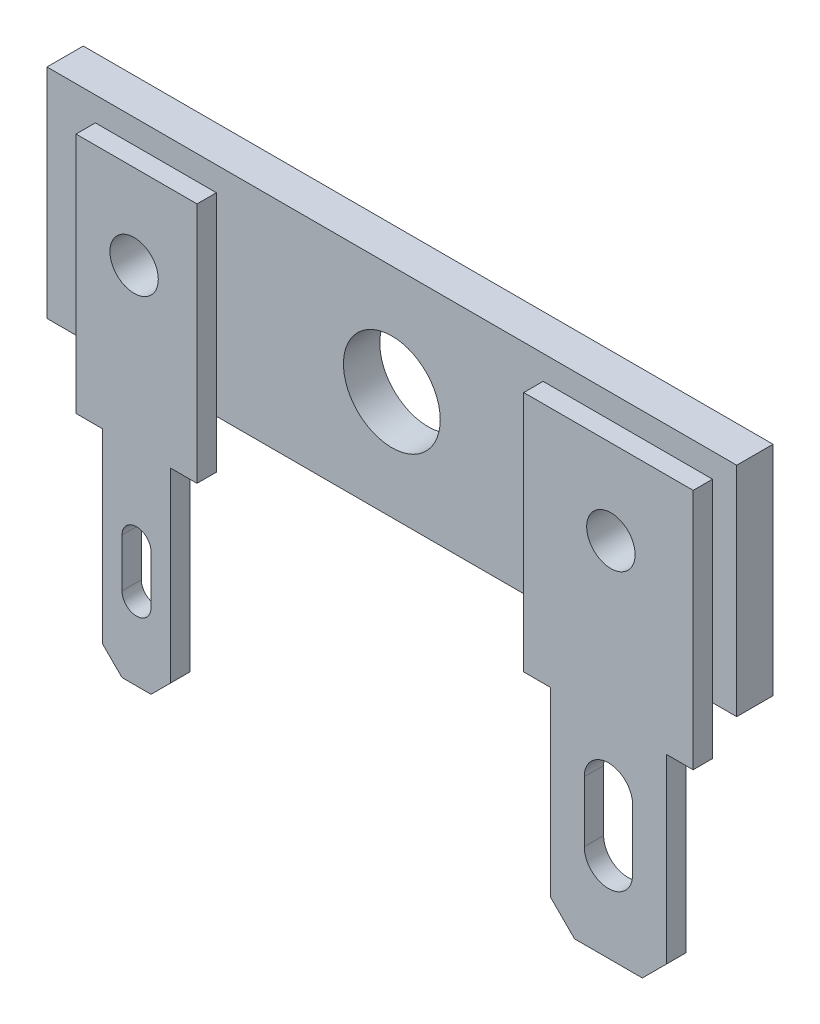
SolidWorks part; units mm, degrees
ref_plane "Plan de face" through (0, 0, 0) normal (0, 0, 1) x (1, 0, 0)
ref_plane "Plan de dessus" through (0, 0, 0) normal (0, 1, 0) x (1, 0, 0)
ref_plane "Plan de droite" through (0, 0, 0) normal (1, 0, 0) x (0, 0, -1)
sketch "Esquisse1" plane through (0, 0, 0) normal (0, 0, 1) x (1, 0, 0)
  line L0 (-54.543, 20.317) -> (-54.543, 30.317)
  line L1 (-54.543, 30.317) -> (-61.543, 30.317)
  line L2 (-61.543, 30.317) -> (-61.543, 20.317)
  line L3 (-61.543, 20.317) -> (-60.443, 20.317)
  line L4 (-60.443, 20.317) -> (-60.443, 12.817)
  line L5 (-60.443, 12.817) -> (-59.443, 11.817)
  line L6 (-59.443, 11.817) -> (-56.643, 11.817)
  line L7 (-56.643, 11.817) -> (-55.643, 12.817)
  line L8 (-55.643, 12.817) -> (-55.643, 20.317)
  line L9 (-55.643, 20.317) -> (-54.543, 20.317)
  line L10 (-75.043, 20.317) -> (-75.043, 30.317)
  line L11 (-75.043, 30.317) -> (-80.043, 30.317)
  line L12 (-80.043, 30.317) -> (-80.043, 20.317)
  line L13 (-80.043, 20.317) -> (-78.943, 20.317)
  line L14 (-78.943, 20.317) -> (-78.943, 12.617)
  line L15 (-78.943, 12.617) -> (-78.143, 11.817)
  line L16 (-78.143, 11.817) -> (-76.943, 11.817)
  line L17 (-76.943, 11.817) -> (-76.143, 12.617)
  line L18 (-76.143, 12.617) -> (-76.143, 20.317)
  line L19 (-76.143, 20.317) -> (-75.043, 20.317)
  line L20 (-82.043, 31.317) -> (-82.043, 22.317)
  line L21 (-82.043, 22.317) -> (-53.543, 22.317)
  line L22 (-53.543, 22.317) -> (-53.543, 31.317)
  line L23 (-53.543, 31.317) -> (-82.043, 31.317)
  line L24 (-76.943, 16.917) -> (-76.943, 14.917)
  line L25 (-78.143, 14.917) -> (-78.143, 16.917)
  line L26 (-57.043, 17.817) -> (-57.043, 15.317)
  line L27 (-59.043, 15.317) -> (-59.043, 17.817)
  arc A0 (-76.943, 14.917) -> (-78.143, 14.917) centre (-77.543, 14.917) cw
  arc A1 (-78.143, 16.917) -> (-76.943, 16.917) centre (-77.543, 16.917) cw
  arc A2 (-59.043, 17.817) -> (-57.043, 17.817) centre (-58.043, 17.817) cw
  arc A3 (-57.043, 15.317) -> (-59.043, 15.317) centre (-58.043, 15.317) cw
  arc A4 (-56.943, 26.817) -> (-58.943, 26.817) centre (-57.943, 26.817) cw
  arc A5 (-58.943, 26.817) -> (-56.943, 26.817) centre (-57.943, 26.817) cw
  arc A6 (-78.643, 26.817) -> (-76.643, 26.817) centre (-77.643, 26.817) cw
  arc A7 (-76.643, 26.817) -> (-78.643, 26.817) centre (-77.643, 26.817) cw
  arc A8 (-65.793, 26.817) -> (-69.793, 26.817) centre (-67.793, 26.817) cw
  arc A9 (-69.793, 26.817) -> (-65.793, 26.817) centre (-67.793, 26.817) cw
extrude "Boss.-Extru.1" add sketch "Esquisse1" along normal blind 1.5 contours L22 L23 L20 L21 L12 L11 L10 L2 L1 L0 A8 A9 | L21 L2 L3 L4 L5 L6 L7 L8 L9 L0 L26 A3 L27 A2 | L21 L12 L13 L14 L15 L16 L17 L18 L19 L10 L25 A1 L24 A0 | L2 L21 L0 L1 A4 A5 | L12 L21 L10 L11 A6 A7 region at (-55.093, 20.4432, 0) region at (-58.043, 22.4233, 0) region at (-54.2442, 26.317, 0) region at (-77.543, 22.4113, 0) region at (-77.543, 17.9428, 0)
sketch "Esquisse2" plane through (0, 0, 1.5) normal (0, 0, 1) x (1, 0, 0)
  line L0 (-80.043, 20.317) -> (-80.043, 30.317)
  line L1 (-75.043, 20.317) -> (-75.043, 30.317)
  line L2 (-80.043, 30.317) -> (-75.043, 30.317)
  line L3 (-61.543, 20.317) -> (-61.543, 30.317)
  line L4 (-54.543, 20.317) -> (-54.543, 30.317)
  line L5 (-61.543, 30.317) -> (-54.543, 30.317)
  line L6 (-76.143, 20.317) -> (-75.043, 20.317) construction
  line L7 (-80.043, 20.317) -> (-78.943, 20.317) construction
  line L8 (-78.943, 20.317) -> (-78.943, 12.617) construction
  line L9 (-78.943, 12.617) -> (-78.143, 11.817) construction
  line L10 (-78.143, 11.817) -> (-76.943, 11.817) construction
  line L11 (-76.943, 11.817) -> (-76.143, 12.617) construction
  line L12 (-76.143, 12.617) -> (-76.143, 20.317) construction
  line L13 (-76.943, 16.917) -> (-76.943, 14.917) construction
  line L14 (-78.143, 14.917) -> (-78.143, 16.917) construction
  line L15 (-61.543, 20.317) -> (-60.443, 20.317) construction
  line L16 (-60.443, 20.317) -> (-60.443, 12.817) construction
  line L17 (-55.643, 12.817) -> (-55.643, 20.317) construction
  line L18 (-55.643, 20.317) -> (-54.543, 20.317) construction
  line L19 (-57.043, 17.817) -> (-57.043, 15.317) construction
  line L20 (-59.043, 15.317) -> (-59.043, 17.817) construction
  line L21 (-76.143, 20.317) -> (-75.043, 20.317)
  line L22 (-80.043, 20.317) -> (-78.943, 20.317)
  line L23 (-78.943, 20.317) -> (-78.943, 12.617)
  line L24 (-78.943, 12.617) -> (-78.143, 11.817)
  line L25 (-78.143, 11.817) -> (-76.943, 11.817)
  line L26 (-76.943, 11.817) -> (-76.143, 12.617)
  line L27 (-76.143, 12.617) -> (-76.143, 20.317)
  line L28 (-76.943, 16.917) -> (-76.943, 14.917)
  line L29 (-78.143, 14.917) -> (-78.143, 16.917)
  line L30 (-61.543, 20.317) -> (-60.443, 20.317)
  line L31 (-60.443, 20.317) -> (-60.443, 12.817)
  line L32 (-55.643, 12.817) -> (-55.643, 20.317)
  line L33 (-55.643, 20.317) -> (-54.543, 20.317)
  line L34 (-57.043, 17.817) -> (-57.043, 15.317)
  line L35 (-59.043, 15.317) -> (-59.043, 17.817)
  arc A0 (-78.143, 14.917) -> (-76.943, 14.917) centre (-77.543, 14.917) ccw construction
  arc A1 (-76.943, 16.917) -> (-78.143, 16.917) centre (-77.543, 16.917) ccw construction
  arc A2 (-59.043, 15.317) -> (-57.043, 15.317) centre (-58.043, 15.317) ccw construction
  arc A3 (-57.043, 17.817) -> (-59.043, 17.817) centre (-58.043, 17.817) ccw construction
  arc A4 (-78.143, 14.917) -> (-76.943, 14.917) centre (-77.543, 14.917) ccw
  arc A5 (-76.943, 16.917) -> (-78.143, 16.917) centre (-77.543, 16.917) ccw
  arc A6 (-59.043, 15.317) -> (-57.043, 15.317) centre (-58.043, 15.317) ccw
  arc A7 (-57.043, 17.817) -> (-59.043, 17.817) centre (-58.043, 17.817) ccw
  circle A8 centre (-57.943, 26.817) radius 1 construction
  circle A9 centre (-77.643, 26.817) radius 1 construction
  circle A10 centre (-57.943, 26.817) radius 1
  circle A11 centre (-77.643, 26.817) radius 1
  line M16 (-61.543, 22.317) -> (-61.543, 20.317)
  line M17 (-61.543, 20.317) -> (-60.443, 20.317)
  line M18 (-60.443, 20.317) -> (-60.443, 12.817)
  line M19 (-60.443, 12.817) -> (-59.443, 11.817)
  line M20 (-59.443, 11.817) -> (-56.643, 11.817)
  line M21 (-56.643, 11.817) -> (-55.643, 12.817)
  line M22 (-55.643, 12.817) -> (-55.643, 20.317)
  line M23 (-55.643, 20.317) -> (-54.543, 20.317)
  line M24 (-54.543, 20.317) -> (-54.543, 22.317)
  line M30 (-80.043, 22.317) -> (-80.043, 20.317)
  line M31 (-80.043, 20.317) -> (-78.943, 20.317)
  line M32 (-78.943, 20.317) -> (-78.943, 12.617)
  line M33 (-78.943, 12.617) -> (-78.143, 11.817)
  line M34 (-78.143, 11.817) -> (-76.943, 11.817)
  line M35 (-76.943, 11.817) -> (-76.143, 12.617)
  line M36 (-76.143, 12.617) -> (-76.143, 20.317)
  line M37 (-76.143, 20.317) -> (-75.043, 20.317)
  line M38 (-75.043, 20.317) -> (-75.043, 22.317)
  line M39 (-78.143, 14.917) -> (-78.143, 16.917)
  arc M40 (-78.143, 16.917) -> (-76.943, 16.917) centre (-77.543, 16.917) cw
  line M41 (-76.943, 16.917) -> (-76.943, 14.917)
  arc M42 (-76.943, 14.917) -> (-78.143, 14.917) centre (-77.543, 14.917) cw
  circle M43 centre (-77.643, 26.817) radius 1
  circle M45 centre (-57.943, 26.817) radius 1
  line M46 (-57.043, 17.817) -> (-57.043, 15.317)
  arc M47 (-57.043, 15.317) -> (-59.043, 15.317) centre (-58.043, 15.317) cw
  line M48 (-59.043, 15.317) -> (-59.043, 17.817)
  arc M49 (-59.043, 17.817) -> (-57.043, 17.817) centre (-58.043, 17.817) cw
extrude "Boss.-Extru.2" add sketch "Esquisse2" along normal blind 0.8 contours L2 L0 L1 M30 M31 M32 M33 M34 M35 M36 M37 M38 M42 M39 M40 M41 M43 | L5 L3 L4 M16 M17 M18 M19 M20 M21 M22 M23 M24 M49 M46 M47 M48 M45 region at (-77.5383, 22.5616, 1.5) region at (-58.0462, 22.2951, 1.5)
sketch "Esquisse3" plane through (-82.043, 0, 0) normal (-1, 0, 0) x (0, 0, 1)
  line L0 (0, 22.317) -> (1.5, 22.317)
  line L1 (1.5, 22.317) -> (1.5, 11.817)
  line L2 (2.3, 11.817) -> (0, 11.817) construction
  line L3 (1.5, 11.817) -> (0, 11.817)
  line L4 (0, 11.817) -> (0, 22.317)
extrude "Enlèv. mat.-Extru.1" cut sketch "Esquisse3" against normal up to surface (28.5 mm away) up to face at (-53.543, 26.817, 0.75)
